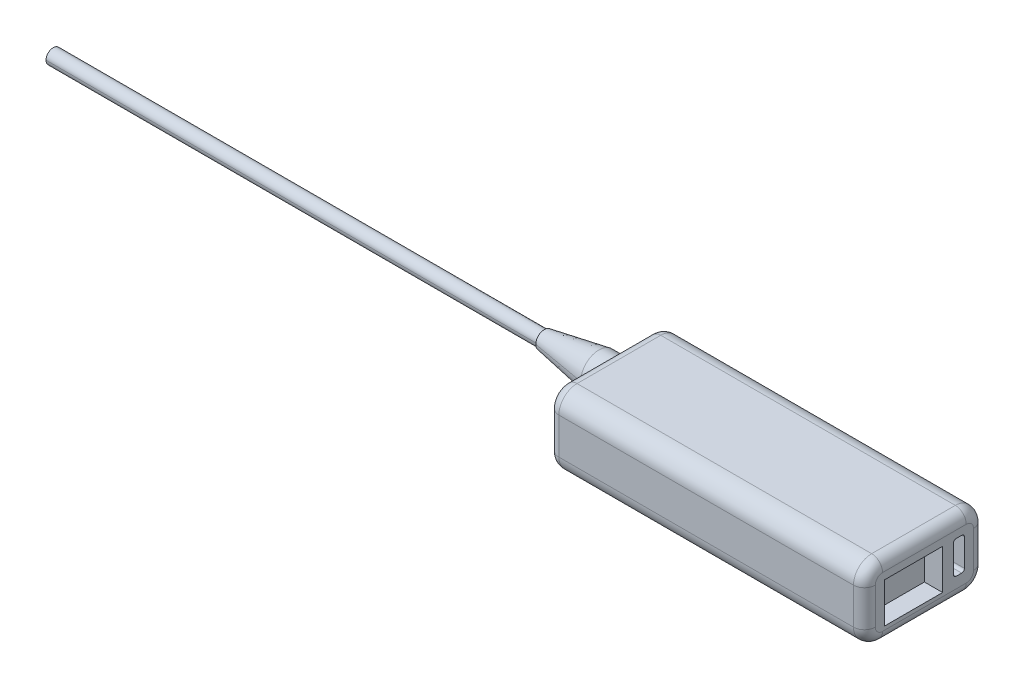
SolidWorks part; units mm, degrees
ref_plane "Front Plane" through (0, 0, 0) normal (0, 0, 1) x (1, 0, 0)
ref_plane "Top Plane" through (0, 0, 0) normal (0, 1, 0) x (1, 0, 0)
ref_plane "Right Plane" through (0, 0, 0) normal (1, 0, 0) x (0, 0, -1)
sketch "Sketch1" plane through (0, 0, 0) normal (0, 1, 0) x (1, 0, 0)
  line L1 (0, 0) -> (87, 0)
  line L2 (0, 0) -> (0, 33)
  line L3 (0, 33) -> (87, 33)
  line L4 (87, 0) -> (87, 33)
  dimension "D1" = 87
  dimension "D2" = 33
extrude "Boss-Extrude1" add sketch "Sketch1" along normal blind 20
sketch "Sketch3" plane through (0, 0, 0) normal (-1, 0, 0) x (0, 0, 1)
  line L1 (-33, 0) -> (-17, 0)
  line L2 (-33, 0) -> (-33, 12)
  line L3 (-33, 12) -> (-17, 12)
  line L4 (-17, 0) -> (-17, 12)
  dimension "D1" = 12
  dimension "D2" = 16
extrude "Cut-Extrude1" cut sketch "Sketch3" against normal blind 9
sketch "Sketch4" plane through (9, 0, 0) normal (-1, 0, 0) x (0, 0, 1)
  line L0 (-25, 12) -> (-25, 0) construction
  line L1 (-17, 12) -> (-33, 12) construction
  line L2 (-33, 0) -> (-17, 0) construction
  line L3 (-33, 6) -> (-17, 6) construction
  line L4 (-33, 12) -> (-33, 0) construction
  line L5 (-17, 0) -> (-17, 12) construction
  circle A0 centre (-25, 6) radius 5
  dimension "D1" = 10
extrude "Boss-Extrude2" add sketch "Sketch4" along normal blind 35
sketch "Sketch5" plane through (-26, 0, 0) normal (-1, 0, 0) x (0, 0, 1)
  circle A0 centre (-25, 6) radius 2
  circle A1 centre (-25, 6) radius 5 construction
  dimension "D1" = 4
extrude "Boss-Extrude3" add sketch "Sketch5" along normal blind 135
sketch "Sketch6" plane through (87, 0, 0) normal (1, 0, 0) x (0, 0, -1)
  line L0 (0, 20) -> (0, 0) construction
  line L1 (5.5, 4) -> (21.5, 4)
  line L2 (5.5, 4) -> (5.5, 15)
  line L3 (5.5, 15) -> (21.5, 15)
  line L4 (21.5, 4) -> (21.5, 15)
  line L5 (0, 0) -> (33, 0) construction
  line L7 (25.25, 15) -> (26.75, 15)
  line L8 (24.5, 14.25) -> (24.5, 6.75)
  line L9 (25.25, 6) -> (26.75, 6)
  line L10 (27.5, 14.25) -> (27.5, 6.75)
  arc A0 (24.5, 6.75) -> (25.25, 6) centre (25.25, 6.75) ccw
  arc A1 (27.5, 6.75) -> (26.75, 6) centre (26.75, 6.75) cw
  arc A2 (26.75, 15) -> (27.5, 14.25) centre (26.75, 14.25) cw
  arc A3 (25.25, 15) -> (24.5, 14.25) centre (25.25, 14.25) ccw
  point P16 (27.5, 6)
  point P19 (27.5, 15)
  point P22 (24.5, 15)
  dimension "D8" = 0.75
  dimension "D1" = 21.5
  dimension "D2" = 15
  dimension "D3" = 11
  dimension "D4" = 16
  dimension "D5" = 3
  dimension "D6" = 3
  dimension "D7" = 9
extrude "Cut-Extrude2" cut sketch "Sketch6" against normal blind 5
fillet "Fillet1" radius 5 4 edges at (43.5, 20, -33) (43.5, 20, 0) (43.5, 0, 0) (48, 0, -33)
fillet "Fillet2" radius 3 15 edges at (0, 13.5, -33) (0, 18.5355, -31.5355) (0, 0, -11) (0, 1.4645, -1.4645) (0, 10, 0) (0, 18.5355, -1.4645) (87, 18.5355, -1.4645) (87, 10, 0) (87, 1.4645, -1.4645) (87, 0, -16.5) (87, 1.4645, -31.5355) (87, 10, -33) (87, 18.5355, -31.5355) (0, 20, -16.5) (87, 20, -16.5)
fillet "Fillet3" radius 1 11 edges at (0, 12, -23.5) (0, 7.5, -17) (0.8787, 12, -32.1213) (0.8787, 0.8787, -17) (6, 12, -33) (6, 0, -17) (9, 12, -25) (9, 6, -17) (9, 0, -22.5) (9, 1.4645, -31.5355) (9, 8.5, -33)
chamfer "Chamfer2" distance 15 angle 10 1 edges at (-26, 6, -20) first distance on face at (-26, 6, -20)
sketch "Sketch7" plane through (82, 0, 0) normal (1, 0, 0) x (0, 0, -1)
  text T0 "ETH"
sketch "Sketch8" plane through (82, 0, 0) normal (1, 0, 0) x (0, 0, -1)
  text T0 "USB-C" font "Century Gothic" height 2
split line "Split Line2"
